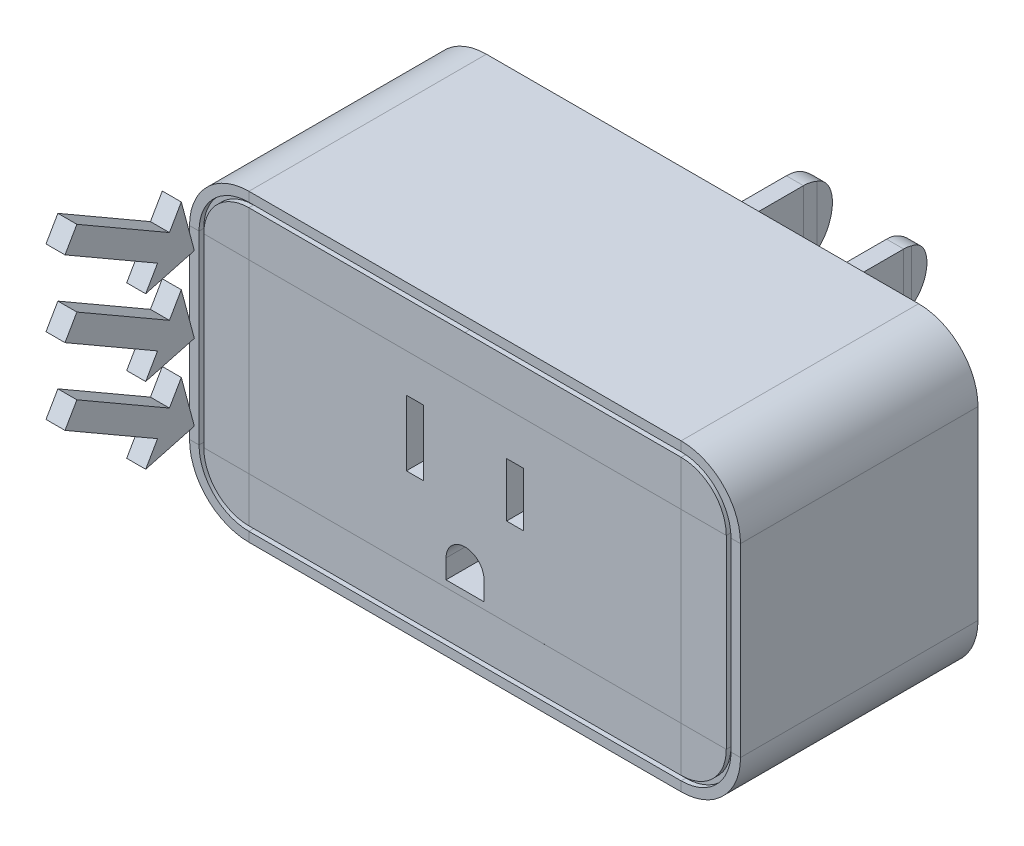
SolidWorks part; units mm, degrees
ref_plane "Front" through (0, 0, 0) normal (0, 0, 1) x (1, 0, 0)
ref_plane "Top" through (0, 0, 0) normal (0, 1, 0) x (1, 0, 0)
ref_plane "Right" through (0, 0, 0) normal (1, 0, 0) x (0, 0, -1)
sketch "Sketch1" plane through (0, 0, 0) normal (0, 0, 1) x (1, 0, 0)
  line L0 (-8.4059, 1.562) -> (65.2541, 1.562) construction
  line L1 (-28.8925, -15.24) -> (28.8925, -15.24)
  line L2 (-28.8925, -15.24) -> (-28.8925, 9.525)
  line L3 (-28.8925, 9.525) -> (28.8925, 9.525)
  line L4 (28.8925, -15.24) -> (28.8925, 9.525)
  line L5 (-5.5562, 0) -> (5.5563, 0) construction
  line L6 (-7.8423, 4.3815) -> (-5.5563, 4.3815) construction
  line L7 (-7.8423, 4.3815) -> (-7.8423, -4.3815) construction
  line L8 (-7.8423, -4.3815) -> (-5.5563, -4.3815) construction
  line L9 (-5.5563, 4.3815) -> (-5.5563, -4.3815) construction
  line L10 (5.5563, 3.7465) -> (7.8423, 3.7465) construction
  line L11 (5.5563, 3.7465) -> (5.5563, -3.4925) construction
  line L12 (5.5563, -3.4925) -> (7.8423, -3.4925) construction
  line L13 (7.8423, 3.7465) -> (7.8423, -3.4925) construction
  line L14 (-2.54, -14.351) -> (2.54, -14.351) construction
  line L15 (-2.54, -14.351) -> (-2.54, -11.811) construction
  line L16 (-2.54, -11.811) -> (2.54, -11.811) construction
  line L17 (2.54, -14.351) -> (2.54, -11.811) construction
  line L18 (0, 9.525) -> (0, 0) construction
  line L19 (0, 0) -> (0, -11.811) construction
  circle A0 centre (-28.8925, 9.525) radius 7.9375 construction
  circle A1 centre (28.8925, -15.24) radius 7.9375 construction
  arc A2 (-2.54, -11.811) -> (2.54, -11.811) centre (0, -11.811) cw construction
  point P7 (-36.83, 9.525)
  point P8 (-28.8925, 17.4625)
  point P9 (28.8925, -23.1775)
  point P10 (36.83, -15.24)
  dimension "D4" = 15.875
  dimension "D10" = 2.54
  dimension "D1" = 73.66
  dimension "D2" = 40.64
  dimension "D3" = 73.66
  dimension "D5" = 2.286
  dimension "D6" = 2.286
  dimension "D7" = 7.239
  dimension "D8" = 8.763
  dimension "D9" = 9.525
  dimension "D11" = 2.54
  dimension "D12" = 21.336
  dimension "D13" = 11.1125
  dimension "D14" = 0.635
extrude "Boss-Extrude1" add sketch "Sketch1" against normal mid plane 31.75
sketch "Sketch2" plane through (0, 0, -15.875) normal (0, 0, -1) x (-1, 0, 0)
  line L0 (28.8925, -15.24) -> (-28.8925, -15.24) construction
  line L1 (28.8925, 9.525) -> (36.83, 9.525)
  line L2 (28.8925, 9.525) -> (28.8925, -15.24)
  line L3 (28.8925, -15.24) -> (36.83, -15.24)
  line L4 (36.83, 9.525) -> (36.83, -15.24)
  line L5 (28.8925, -15.24) -> (-28.8925, -15.24)
  line L6 (28.8925, -15.24) -> (28.8925, -23.1775)
  line L7 (28.8925, -23.1775) -> (-28.8925, -23.1775)
  line L8 (-28.8925, -15.24) -> (-28.8925, -23.1775)
  line L10 (-28.8925, -15.24) -> (-36.83, -15.24)
  line L11 (-28.8925, -15.24) -> (-28.8925, 9.525)
  line L12 (-28.8925, 9.525) -> (-36.83, 9.525)
  line L13 (-36.83, -15.24) -> (-36.83, 9.525)
  line L14 (-28.8925, 9.525) -> (28.8925, 9.525)
  line L15 (-28.8925, 9.525) -> (-28.8925, 17.4625)
  line L16 (-28.8925, 17.4625) -> (28.8925, 17.4625)
  line L17 (28.8925, 9.525) -> (28.8925, 17.4625)
  line M26 (28.8925, -15.24) -> (28.8925, 9.525)
  line M27 (28.8925, 9.525) -> (-28.8925, 9.525)
  line M28 (-28.8925, 9.525) -> (-28.8925, -15.24)
  line M29 (-28.8925, -15.24) -> (28.8925, -15.24)
extrude "Boss-Extrude2" add sketch "Sketch2" against normal up to surface (31.75 mm away) separate body contours L10 L13 L12 | L8 L6 L7 | L17 L15 L16 | L1 L4 L3 | L13 L10 L12 M28 | L17 L16 L15 M27 | L4 L1 L3 M26 | L8 L7 L6 M29 region at (-32.8613, -2.8575, -15.875) region at (0, 13.4938, -15.875) region at (0, -19.2087, -15.875) region at (32.8612, -2.8575, -15.875) up to face at (0, -2.8575, 15.875)
sketch "Sketch3" plane through (0, 0, 15.875) normal (0, 0, 1) x (1, 0, 0)
  line L1 (-7.8423, 4.3815) -> (-5.5563, 4.3815)
  line L2 (-7.8423, 4.3815) -> (-7.8423, -4.3815)
  line L3 (-7.8423, -4.3815) -> (-5.5563, -4.3815)
  line L4 (-5.5563, 4.3815) -> (-5.5563, -4.3815)
  line L5 (5.5563, 3.7465) -> (7.8423, 3.7465)
  line L6 (5.5563, 3.7465) -> (5.5563, -3.4925)
  line L7 (5.5563, -3.4925) -> (7.8423, -3.4925)
  line L8 (7.8423, 3.7465) -> (7.8423, -3.4925)
  line L9 (-2.54, -14.351) -> (2.54, -14.351)
  line L10 (-2.54, -14.351) -> (-2.54, -11.811)
  line L11 (-2.54, -11.811) -> (2.54, -11.811)
  line L12 (2.54, -14.351) -> (2.54, -11.811)
extrude "Cut-Extrude1" cut sketch "Sketch3" against normal blind 19.05
sketch "Sketch5" plane through (0, 0, -15.875) normal (0, 0, -1) x (-1, 0, 0)
  line L0 (-5.5563, 3.7465) -> (-7.8423, 3.7465) construction
  line L5 (-7.8423, 3.7465) -> (-5.5563, 3.7465)
  line L6 (-7.8423, 3.7465) -> (-7.8423, -3.4925)
  line L7 (-7.8423, -3.4925) -> (-5.5563, -3.4925)
  line L8 (-5.5563, 3.7465) -> (-5.5563, -3.4925)
  line L9 (5.5563, 4.3815) -> (7.8423, 4.3815)
  line L10 (5.5563, 4.3815) -> (5.5563, -4.3815)
  line L11 (5.5563, -4.3815) -> (7.8423, -4.3815)
  line L12 (7.8423, 4.3815) -> (7.8423, -4.3815)
  line L13 (-7.8423, 3.7465) -> (-7.8423, -3.4925) construction
  line L14 (-5.5563, 3.7465) -> (-5.5563, -3.4925) construction
  line L15 (-5.5563, -3.4925) -> (-7.8423, -3.4925) construction
  line L16 (5.5563, 4.3815) -> (5.5563, -4.3815) construction
  line L17 (7.8423, 4.3815) -> (5.5563, 4.3815) construction
  line L18 (7.8423, 4.3815) -> (7.8423, -4.3815) construction
  line L19 (7.8423, -4.3815) -> (5.5563, -4.3815) construction
extrude "Boss-Extrude3" add sketch "Sketch5" along normal blind 19.05
sketch "Sketch6" plane through (0, 0, 15.875) normal (0, 0, 1) x (1, 0, 0)
  line L0 (-36.83, 9.525) -> (-28.8925, 9.525)
  line L1 (-28.8925, 9.525) -> (-28.8925, 17.4625)
  line L2 (0, -23.1775) -> (0, 17.4625) construction
  line L5 (28.8925, 9.525) -> (28.8925, 17.4625)
  line L6 (36.83, 9.525) -> (28.8925, 9.525)
  line L7 (-36.83, -2.8575) -> (0, -2.8575) construction
  line L8 (-36.83, -15.24) -> (-36.83, 9.525) construction
  line L9 (-28.8925, -15.24) -> (-28.8925, -23.1775)
  line L10 (-36.83, -15.24) -> (-28.8925, -15.24)
  line L11 (36.83, -15.24) -> (28.8925, -15.24)
  line L12 (28.8925, -15.24) -> (28.8925, -23.1775)
  line L13 (-28.8925, 17.4625) -> (28.8925, 17.4625) construction
  line L14 (28.8925, 9.525) -> (-28.8925, 9.525) construction
  line L15 (-28.8925, 17.4625) -> (28.8925, 17.4625) construction
  line L16 (-36.83, 9.525) -> (-28.8925, 9.525) construction
  line L17 (-28.8925, 17.4625) -> (-28.8925, 9.525) construction
  arc A0 (-28.8925, 17.4625) -> (-36.83, 9.525) centre (-28.8925, 9.525) ccw
  arc A1 (28.8925, 17.4625) -> (36.83, 9.525) centre (28.8925, 9.525) cw
  arc A2 (-28.8925, -23.1775) -> (-36.83, -15.24) centre (-28.8925, -15.24) cw
  arc A3 (28.8925, -23.1775) -> (36.83, -15.24) centre (28.8925, -15.24) ccw
extrude "Boss-Extrude4" add sketch "Sketch6" against normal up to surface (31.75 mm away) up to face at (0, -2.8575, -15.875)
sketch "Sketch11" plane through (-36.83, 0, 0) normal (-1, 0, 0) x (0, 0, 1)
  line L0 (-15.875, -2.8575) -> (0, -2.8575) construction
  line L2 (0, -2.8575) -> (0, 9.525) construction
  line L4 (15.875, 9.525) -> (-15.875, 9.525) construction
  line L5 (-15.875, 9.525) -> (-15.875, -15.24) construction
  circle A0 centre (0, -2.8575) radius 4.7625
  dimension "D1" = 9.525
extrude "Cut-Extrude5" cut sketch "Sketch11" against normal blind 6.35
ref_plane "Plane1" through (0, -2.8575, 0) normal (0, 1, 0) x (1, 0, 0)
sketch "Sketch12" plane through (-30.48, 0, 0) normal (-1, 0, 0) x (0, 0, 1)
  circle A0 centre (0, -2.8575) radius 4.572
  dimension "D1" = 9.144
extrude "Boss-Extrude6" add sketch "Sketch12" along normal blind 6.35
sketch "Sketch14" plane through (-7.8423, 0, 0) normal (-1, 0, 0) x (0, 0, 1)
  line L1 (-34.925, 4.3815) -> (-15.875, 4.3815) construction
  line L2 (-34.925, -4.3815) -> (-15.875, -4.3815) construction
  line L3 (-34.925, -4.3815) -> (-34.925, 4.3815) construction
  line L4 (-34.925, 4.3815) -> (-34.925, -4.3815)
  circle A0 centre (-34.925, 0) radius 4.3815
  line M4 (-34.925, 4.3815) -> (-34.925, -4.3815)
extrude "Boss-Extrude7" add sketch "Sketch14" against normal up to surface (2.286 mm away) separate body contours A0 M4 region at (-7.8423, 0, -36.7846) up to face at (-5.5563, 0, -25.4)
sketch "Sketch15" plane through (7.8423, 0, 0) normal (1, 0, 0) x (0, 0, -1)
  line L0 (34.925, 3.7465) -> (34.925, -3.4925) construction
  line L1 (34.925, 3.7465) -> (34.925, -3.4925)
  circle A0 centre (34.925, 0.127) radius 3.6195
  line M4 (34.925, -3.4925) -> (34.925, 3.7465)
extrude "Boss-Extrude8" add sketch "Sketch15" against normal up to surface (2.286 mm away) separate body contours A0 M4 region at (7.8423, 0.127, -36.4612) up to face at (5.5563, 0.127, -25.4)
sketch "Sketch16" plane through (0, 0, -15.875) normal (0, 0, -1) x (-1, 0, 0)
  circle A0 centre (0, -11.811) radius 2.54
  arc A1 (2.54, -11.811) -> (-2.54, -11.811) centre (0, -11.811) ccw construction
extrude "Boss-Extrude9" add sketch "Sketch16" along normal blind 19.05
sketch "Sketch18" plane through (0, 0, 15.875) normal (0, 0, 1) x (1, 0, 0)
  line L0 (2.54, -11.811) -> (-2.54, -11.811) construction
  circle A0 centre (0, -11.811) radius 2.54
extrude "Cut-Extrude6" cut sketch "Sketch18" against normal blind 19.05
sketch "Sketch13" plane through (0, 0, 0) normal (0, 0, 1) x (1, 0, 0)
  line L0 (-56.0229, -2.8575) -> (-36.83, -2.8575) construction
  line L1 (-36.83, -15.24) -> (-36.83, 9.525) construction
  line L2 (-36.322, -2.8575) -> (-75.7237, -2.8575)
  circle A0 centre (-56.0229, -2.8575) radius 19.7009
  point P2 (-36.322, -2.8575)
  point P6 (-36.83, 1.5875)
  point P7 (-36.83, -7.3025)
  dimension "D1" = 0.508
  dimension "D2" = 8.89
revolve "Cut-Revolve2" cut sketch "Sketch13" angle 360 about L0 region at (-56.0229, 5.5038, 0)
sketch "Sketch17" plane through (0, 0, 0) normal (1, 0, 0) x (0, 0, -1)
  line L0 (34.925, -11.811) -> (37.465, -11.811)
  line L1 (34.925, -9.271) -> (34.925, -11.811)
  line L3 (34.925, -14.351) -> (34.925, -9.271) construction
  line L4 (34.925, -9.271) -> (15.875, -9.271) construction
  arc A0 (37.465, -11.811) -> (34.925, -9.271) centre (34.925, -11.811) ccw
revolve "Revolve1" add sketch "Sketch17" angle 360 about L0
ref_plane "Plane2" through (6.6993, 0, 0) normal (-1, 0, 0) x (0, 0, 1)
sketch "Sketch19" plane through (0, 3.7465, 0) normal (0, 1, 0) x (1, 0, 0)
  line L0 (-7.3343, 39.3065) -> (-7.8423, 36.7665)
  line L2 (-7.8423, 34.925) -> (-7.8423, 15.875) construction
  line L3 (-7.8423, 36.7665) -> (-7.8423, 39.3065)
  line L4 (-7.8423, 39.3065) -> (-7.3343, 39.3065)
  line L5 (-6.0643, 39.3065) -> (-5.5563, 36.7665)
  line L6 (-5.5563, 34.925) -> (-5.5563, 15.875) construction
  line L7 (-5.5563, 36.7665) -> (-5.5563, 39.3065)
  line L8 (-5.5563, 39.3065) -> (-6.0643, 39.3065)
  line L9 (6.0643, 38.5445) -> (5.5562, 36.0045)
  line L11 (5.5563, 34.925) -> (5.5563, 15.875) construction
  line L12 (5.5562, 36.0045) -> (5.5563, 38.5445)
  line L13 (5.5563, 38.5445) -> (6.0643, 38.5445)
  line L14 (7.3343, 38.5445) -> (7.8423, 36.0045)
  line L15 (7.8423, 34.925) -> (7.8423, 15.875) construction
  line L16 (7.8423, 36.0045) -> (7.8423, 38.5445)
  line L17 (7.8423, 38.5445) -> (7.3343, 38.5445)
  line L18 (-7.8423, 39.3065) -> (-7.8423, 34.925) construction
  line L19 (5.5563, 38.5445) -> (5.5563, 34.925) construction
  line L20 (7.8423, 34.925) -> (7.8423, 38.5445) construction
  dimension "D1" = 1.27
  dimension "D2" = 2.54
extrude "Cut-Extrude7" cut sketch "Sketch19" against normal through all both and the other way through all
sketch "Sketch9" plane through (0, 0, 15.875) normal (0, 0, 1) x (1, 0, 0)
  line L8 (-28.8925, 17.4625) -> (28.8925, 17.4625) construction
  line L9 (-36.83, -15.24) -> (-36.83, 9.525) construction
  line L10 (28.8925, -23.1775) -> (-28.8925, -23.1775) construction
  line L11 (36.83, 9.525) -> (36.83, -15.24) construction
  line L12 (35.56, -15.24) -> (35.56, 9.525)
  line L13 (-28.8925, -21.9075) -> (28.8925, -21.9075)
  line L14 (-35.56, 9.525) -> (-35.56, -15.24)
  line L15 (28.8925, 16.1925) -> (-28.8925, 16.1925)
  line L24 (-28.8925, 9.525) -> (-28.8925, 17.4625) construction
  line L25 (-36.83, 9.525) -> (-28.8925, 9.525) construction
  line L26 (-28.8925, -15.24) -> (-36.83, -15.24) construction
  line L27 (-28.8925, -23.1775) -> (-28.8925, -15.24) construction
  line L28 (28.8925, 17.4625) -> (28.8925, 9.525) construction
  line L29 (36.83, 9.525) -> (28.8925, 9.525) construction
  line L30 (36.83, -15.24) -> (28.8925, -15.24) construction
  line L31 (28.8925, -15.24) -> (28.8925, -23.1775) construction
  arc A12 (35.56, 9.525) -> (28.8925, 16.1925) centre (28.8925, 9.525) ccw
  arc A13 (28.8925, -21.9075) -> (35.56, -15.24) centre (28.8925, -15.24) ccw
  arc A14 (-35.56, -15.24) -> (-28.8925, -21.9075) centre (-28.8925, -15.24) ccw
  arc A15 (-28.8925, 16.1925) -> (-35.56, 9.525) centre (-28.8925, 9.525) ccw
  dimension "D1" = 1.27
  dimension "D3" = 1.27
  dimension "D4" = 1.27
  dimension "D5" = 1.27
ref_plane "Plane3" through (0, 0, 0) normal (-1, 0, 0) x (0, 0, 1)
sketch "Sketch10" plane through (0, 0, 0) normal (1, 0, 0) x (0, 0, -1)
  line L1 (-15.875, 16.1925) -> (-15.24, 16.1925)
  line L2 (-15.875, 16.1925) -> (-15.875, 15.5575)
  line L3 (-15.875, 15.5575) -> (-15.24, 15.5575)
  line L4 (-15.24, 16.1925) -> (-15.24, 15.5575)
  dimension "D1" = 0.635
sweep "Cut-Sweep1" cut profiles "Sketch10" path "Sketch9"
sketch "Sketch21" plane through (-35.56, 0, 0) normal (-1, 0, 0) x (0, 0, 1)
  line L0 (16.5023, 7.5711) -> (23.008, 5.8279)
  line L1 (23.008, 5.8279) -> (21.4205, 8.5775)
  line L2 (21.4205, 8.5775) -> (33.7938, 15.7213)
  line L3 (33.7938, 15.7213) -> (32.2063, 18.4709)
  line L4 (32.2063, 18.4709) -> (19.833, 11.3272)
  line L5 (19.833, 11.3272) -> (18.2455, 14.0768)
  line L6 (18.2455, 14.0768) -> (16.5023, 7.5711)
  line L7 (16.5023, 7.5711) -> (33.0001, 17.0961) construction
  line L8 (16.5023, -2.5889) -> (23.008, -4.3321)
  line L9 (23.008, -4.3321) -> (21.4205, -1.5825)
  line L10 (21.4205, -1.5825) -> (33.7938, 5.5613)
  line L11 (33.7938, 5.5613) -> (32.2063, 8.3109)
  line L12 (32.2063, 8.3109) -> (19.833, 1.1672)
  line L13 (19.833, 1.1672) -> (18.2455, 3.9168)
  line L14 (18.2455, 3.9168) -> (16.5023, -2.5889)
  line L15 (16.5023, -2.5889) -> (33.0001, 6.9361) construction
  line L16 (16.5023, -12.7489) -> (23.008, -14.4921)
  line L17 (23.008, -14.4921) -> (21.4205, -11.7425)
  line L18 (21.4205, -11.7425) -> (33.7938, -4.5987)
  line L19 (33.7938, -4.5987) -> (32.2063, -1.8491)
  line L20 (32.2063, -1.8491) -> (19.833, -8.9928)
  line L21 (19.833, -8.9928) -> (18.2455, -6.2432)
  line L22 (18.2455, -6.2432) -> (16.5023, -12.7489)
  line L23 (16.5023, -12.7489) -> (33.0001, -3.2239) construction
  dimension "D1" = 3
extrude "Boss-Extrude12" add sketch "Sketch21" along normal blind 2.54 separate body
